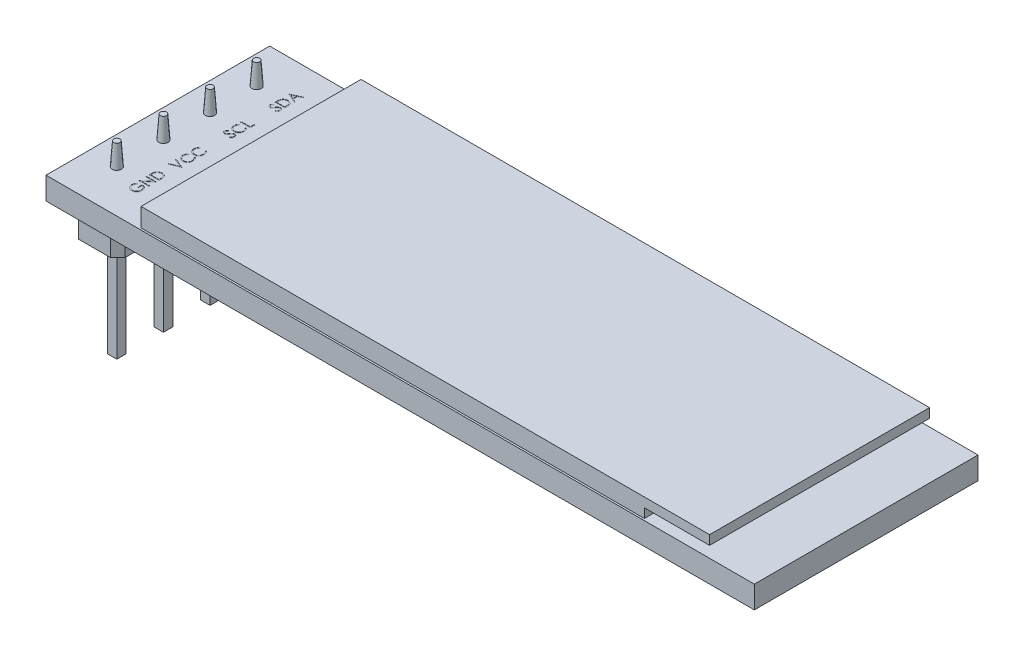
SolidWorks part; units mm, degrees
ref_plane "Alzado" through (0, 0, 0) normal (0, 0, 1) x (1, 0, 0)
ref_plane "Planta" through (0, 0, 0) normal (0, 1, 0) x (1, 0, 0)
ref_plane "Vista lateral" through (0, 0, 0) normal (1, 0, 0) x (0, 0, -1)
sketch "Croquis1" plane through (0, 0, 0) normal (0, 1, 0) x (1, 0, 0)
  line L1 (-19, 6) -> (19, 6)
  line L2 (-19, 6) -> (-19, -6)
  line L3 (-19, -6) -> (19, -6)
  line L4 (19, 6) -> (19, -6)
  line L5 (-19, 6) -> (19, -6) construction
  line L6 (-19, -6) -> (19, 6) construction
  point P0 (0, 0)
  dimension "D1" = 38
  dimension "D2" = 12
extrude "Saliente-Extruir1" add sketch "Croquis1" along normal blind 1.2
sketch "Croquis2" plane through (0, 1.2, 0) normal (0, 1, 0) x (1, 0, 0)
  line L0 (19, 6) -> (-19, 6) construction
  line L1 (-19, 6) -> (-19, -6) construction
  circle A0 centre (-17.5, 3.8) radius 0.25
  circle A1 centre (-17.5, 1.3) radius 0.25
  circle A2 centre (-17.5, -1.2) radius 0.25
  circle A3 centre (-17.5, -3.7) radius 0.25
  dimension "D1" = 0.5
  dimension "D2" = 2.2
  dimension "D3" = 1.5
  dimension "D4" = 4
extrude "Saliente-Extruir2" add sketch "Croquis2" along normal blind 1.2 draft 4
sketch "Croquis3" plane through (0, 0, 0) normal (0, -1, 0) x (1, 0, 0)
  line L1 (-18.75, -5) -> (-16.25, -5)
  line L2 (-18.75, -5) -> (-18.75, -2.6)
  line L3 (-18.75, -2.6) -> (-16.25, -2.6)
  line L4 (-16.25, -5) -> (-16.25, -2.6)
  line L5 (-18.75, -5) -> (-16.25, -2.6) construction
  line L6 (-18.75, -2.6) -> (-16.25, -5) construction
  point P0 (-17.5, -3.8)
  dimension "D1" = 2.4
  dimension "D2" = 2.5
extrude "Saliente-Extruir3" add sketch "Croquis3" along normal blind 2 contours L2 L1 L4 L3
pattern_linear "MatrizL1" count 4 spacing 2.5 along (0, 0, 1) of "Saliente-Extruir3"
sketch "Croquis4" plane through (0, -2, 0) normal (0, -1, 0) x (1, 0, 0)
  line L0 (-17.75, -1.55) -> (-17.75, -1.05)
  line L1 (-17.75, -4.05) -> (-17.25, -4.05)
  line L2 (-17.75, -4.05) -> (-17.75, -3.55)
  line L3 (-17.75, -3.55) -> (-17.25, -3.55)
  line L4 (-17.25, -4.05) -> (-17.25, -3.55)
  line L5 (-17.75, -4.05) -> (-17.25, -3.55) construction
  line L6 (-17.75, -3.55) -> (-17.25, -4.05) construction
  line L7 (-17.75, -1.55) -> (-17.25, -1.55)
  line L8 (-17.25, -1.55) -> (-17.25, -1.05)
  line L9 (-17.75, -1.05) -> (-17.25, -1.05)
  line L10 (-17.75, 0.95) -> (-17.75, 1.45)
  line L11 (-17.75, 0.95) -> (-17.25, 0.95)
  line L12 (-17.25, 0.95) -> (-17.25, 1.45)
  line L13 (-17.75, 1.45) -> (-17.25, 1.45)
  line L14 (-17.75, 3.45) -> (-17.75, 3.95)
  line L15 (-17.75, 3.45) -> (-17.25, 3.45)
  line L16 (-17.25, 3.45) -> (-17.25, 3.95)
  line L17 (-17.75, 3.95) -> (-17.25, 3.95)
  point P0 (-17.5, -3.8)
  dimension "D1" = 0.5
  dimension "D2" = 0.5
  dimension "D3" = 4
extrude "Saliente-Extruir4" add sketch "Croquis4" along normal blind 5.5
chamfer "Chaflán1" distance 0.4 angle 45 16 edges at (-16.25, -1, 4.9) (-16.25, -1, 2.5) (-16.25, -1, 2.4) (-16.25, -1, 0) (-18.75, -1, 4.9) (-18.75, -1, 2.5) (-18.75, -1, 2.4) (-18.75, -1, 0) (-18.75, -1, -0.1) (-18.75, -1, -2.5) (-18.75, -1, -2.6) (-16.25, -1, -0.1) (-16.25, -1, -2.5) (-16.25, -1, -2.6) (-16.25, -1, -5) (-18.75, -1, -5)
sketch "Croquis5" plane through (0, 0, 0) normal (0, -1, 0) x (1, 0, 0)
  line L0 (19, -6) -> (-19, -6) construction
  line L1 (4.5, -5.3) -> (3, -5.3)
  line L2 (4.5, -5.3) -> (4.5, -4.5)
  line L3 (4.5, -4.5) -> (3, -4.5)
  line L4 (3, -5.3) -> (3, -4.5)
  line L5 (4.5, -5.3) -> (3, -4.5) construction
  line L6 (4.5, -4.5) -> (3, -5.3) construction
  line L7 (19, 6) -> (19, -6) construction
  line L8 (4.5, -3.9) -> (4.5, -3.1)
  line L9 (4.5, -3.9) -> (3, -3.9)
  line L10 (3, -3.9) -> (3, -3.1)
  line L11 (4.5, -3.1) -> (3, -3.1)
  line L12 (4.5, -2.5) -> (4.5, -1.7)
  line L13 (4.5, -2.5) -> (3, -2.5)
  line L14 (3, -2.5) -> (3, -1.7)
  line L15 (4.5, -1.7) -> (3, -1.7)
  line L16 (4.5, -1.1) -> (4.5, -0.3)
  line L17 (4.5, -1.1) -> (3, -1.1)
  line L18 (3, -1.1) -> (3, -0.3)
  line L19 (4.5, -0.3) -> (3, -0.3)
  line L20 (4.5, 0.3) -> (4.5, 1.1)
  line L21 (4.5, 0.3) -> (3, 0.3)
  line L22 (3, 0.3) -> (3, 1.1)
  line L23 (4.5, 1.1) -> (3, 1.1)
  line L24 (4.5, 1.7) -> (4.5, 2.5)
  line L25 (4.5, 1.7) -> (3, 1.7)
  line L26 (3, 1.7) -> (3, 2.5)
  line L27 (4.5, 2.5) -> (3, 2.5)
  line L28 (4.5, 3.1) -> (4.5, 3.9)
  line L29 (4.5, 3.1) -> (3, 3.1)
  line L30 (3, 3.1) -> (3, 3.9)
  line L31 (4.5, 3.9) -> (3, 3.9)
  line L32 (4.5, 4.5) -> (4.5, 5.3)
  line L33 (4.5, 4.5) -> (3, 4.5)
  line L34 (3, 4.5) -> (3, 5.3)
  line L35 (4.5, 5.3) -> (3, 5.3)
  line L36 (-2, -1.9) -> (-2, -1.1)
  line L37 (-2, -3.3) -> (-3.5, -3.3)
  line L38 (-2, -3.3) -> (-2, -2.5)
  line L39 (-2, -2.5) -> (-3.5, -2.5)
  line L40 (-3.5, -3.3) -> (-3.5, -2.5)
  line L41 (-2, -3.3) -> (-3.5, -2.5) construction
  line L42 (-2, -2.5) -> (-3.5, -3.3) construction
  line L43 (-2, -1.9) -> (-3.5, -1.9)
  line L44 (-3.5, -1.9) -> (-3.5, -1.1)
  line L45 (-2, -1.1) -> (-3.5, -1.1)
  line L46 (-2, -0.5) -> (-2, 0.3)
  line L47 (-2, -0.5) -> (-3.5, -0.5)
  line L48 (-3.5, -0.5) -> (-3.5, 0.3)
  line L49 (-2, 0.3) -> (-3.5, 0.3)
  line L50 (-2, 0.9) -> (-2, 1.7)
  line L51 (-2, 0.9) -> (-3.5, 0.9)
  line L52 (-3.5, 0.9) -> (-3.5, 1.7)
  line L53 (-2, 1.7) -> (-3.5, 1.7)
  line L54 (-2, 2.3) -> (-2, 3.1)
  line L55 (-2, 2.3) -> (-3.5, 2.3)
  line L56 (-3.5, 2.3) -> (-3.5, 3.1)
  line L57 (-2, 3.1) -> (-3.5, 3.1)
  point P0 (3.75, -4.9)
  point P9 (-2.75, -2.9)
  dimension "D1" = 0.7
  dimension "D2" = 0.8
  dimension "D3" = 14.5
  dimension "D4" = 1.5
  dimension "D5" = 8
  dimension "D6" = 5
  dimension "D7" = 2.7
  dimension "D8" = 1.5
  dimension "D9" = 0.8
  dimension "D10" = 5
extrude "Saliente-Extruir5" add sketch "Croquis5" along normal blind 0.7 separate body
sketch "Croquis6" plane through (0, -0.7, 0) normal (0, -1, 0) x (1, 0, 0)
  line L0 (3, -0.3) -> (3, -1.1) construction
  line L1 (4.5, -1.1) -> (3, -1.1)
  line L2 (4.5, -1.1) -> (4.5, -0.3)
  line L3 (4.5, -0.3) -> (3, -0.3)
  line L4 (3, -1.1) -> (3, -0.3)
  line L5 (4.5, -1.1) -> (3, -0.3) construction
  line L6 (4.5, -0.3) -> (3, -1.1) construction
  line L7 (4.5, -0.3) -> (3, -0.3) construction
  line L8 (-2, -2.5) -> (-3.5, -2.5) construction
  line L9 (-2, -3.3) -> (-3.5, -3.3)
  line L10 (-2, -3.3) -> (-2, -2.5)
  line L11 (-2, -2.5) -> (-3.5, -2.5)
  line L12 (-3.5, -3.3) -> (-3.5, -2.5)
  line L13 (-2, -3.3) -> (-3.5, -2.5) construction
  line L14 (-2, -2.5) -> (-3.5, -3.3) construction
  line L15 (-3.5, -2.5) -> (-3.5, -3.3) construction
  line L16 (-3.5, 0.3) -> (-3.5, -0.5) construction
  line L17 (-2, -1.9) -> (-3.5, -1.9)
  line L18 (-2, -1.9) -> (-2, -1.1)
  line L19 (-2, -1.1) -> (-3.5, -1.1)
  line L20 (-3.5, -1.9) -> (-3.5, -1.1)
  line L21 (-2, -1.9) -> (-3.5, -1.1) construction
  line L22 (-2, -1.1) -> (-3.5, -1.9) construction
  line L23 (-2, -0.5) -> (-3.5, -0.5)
  line L24 (-2, -0.5) -> (-2, 0.3)
  line L25 (-2, 0.3) -> (-3.5, 0.3)
  line L26 (-3.5, -0.5) -> (-3.5, 0.3)
  line L27 (-2, -0.5) -> (-3.5, 0.3) construction
  line L28 (-2, 0.3) -> (-3.5, -0.5) construction
  line L29 (-2, 0.3) -> (-3.5, 0.3) construction
  point P0 (3.75, -0.7)
  point P9 (-2.75, -2.9)
  point P18 (-2.75, -1.5)
  point P24 (-2.75, -0.1)
extrude "Cortar-Extruir1" cut sketch "Croquis6" against normal blind 0.4
sketch "Croquis7" plane through (0, -0.7, 0) normal (0, -1, 0) x (1, 0, 0)
  line L0 (-2.75, 1.7) -> (-2.75, 1.0081) construction
  line L1 (-2, 1.7) -> (-3.5, 1.7) construction
  line L2 (-2, 1.3) -> (-2.9455, 1.3) construction
  line L3 (-2, 0.9) -> (-2, 1.7) construction
  line L4 (-3.5, 0.9) -> (-2, 0.9) construction
  line L5 (-3.5, 1.7) -> (-2, 1.7)
  line L6 (-3.5, 1.7) -> (-3.5, 0.9)
  line L7 (-3.5, 0.9) -> (-2, 0.9)
  line L8 (-2, 1.7) -> (-2, 0.9)
  line L9 (-3.5, 1.7) -> (-2, 0.9) construction
  line L10 (-3.5, 0.9) -> (-2, 1.7) construction
  point P8 (-2.75, 1.3)
extrude "Cortar-Extruir2" cut sketch "Croquis7" against normal blind 0.3
sketch "Croquis8" plane through (0, 0, 0) normal (0, -1, 0) x (1, 0, 0)
  line L0 (-19, 6) -> (19, 6) construction
  line L1 (-9.5, 0.5) -> (-10.5, 0.5)
  line L2 (-9.5, 0.5) -> (-9.5, 3)
  line L3 (-9.5, 3) -> (-10.5, 3)
  line L4 (-10.5, 0.5) -> (-10.5, 3)
  line L5 (-9.5, 0.5) -> (-10.5, 3) construction
  line L6 (-9.5, 3) -> (-10.5, 0.5) construction
  line L7 (-19, -6) -> (-19, 6) construction
  point P0 (-10, 1.75)
  dimension "D1" = 3
  dimension "D2" = 8.5
  dimension "D3" = 2.5
  dimension "D4" = 1
extrude "Saliente-Extruir6" add sketch "Croquis8" along normal blind 1
ref_plane "Plano1" through (0, 0, 0.62) normal (0, 0, 1) x (1, 0, 0)
sketch "Croquis9" plane through (0, 0, 0.62) normal (0, 0, 1) x (1, 0, 0)
  line L0 (-9.5, -0.2801) -> (-9.3251, -0.2801)
  line L1 (-9.5, -1) -> (-9.5, 0) construction
  line L2 (-9.3051, -0.2601) -> (-9.3051, 0)
  line L3 (-19, 0) -> (19, 0) construction
  line L4 (-9.5, -0.2432) -> (-9.3639, -0.2432)
  line L5 (-9.3439, -0.2232) -> (-9.3439, 0)
  line L6 (-9.5, -0.2432) -> (-9.5, -0.2801)
  line L7 (-9.3439, 0) -> (-9.3051, 0)
  arc A0 (-9.3051, -0.2601) -> (-9.3251, -0.2801) centre (-9.3251, -0.2601) cw
  arc A1 (-9.3639, -0.2432) -> (-9.3439, -0.2232) centre (-9.3639, -0.2232) ccw
  dimension "D1" = 0.02
extrude "Saliente-Extruir7" add sketch "Croquis9" along normal blind 0.9
pattern_linear "MatrizL2" count 2 spacing 1.3 along (0, 0, 1) of "Saliente-Extruir7"
ref_plane "Plano2" through (0, 0, 1.75) normal (0, 0, 1) x (1, 0, 0)
sketch "Croquis12" plane through (0, 0, 1.75) normal (0, 0, 1) x (1, 0, 0)
  line L1 (-10.5, -0.2801) -> (-10.5, -0.2432)
  line L6 (-10, 0) -> (-10, -0.6809) construction
  line L7 (-10.5, 0) -> (-9.5, 0) construction
  line L8 (-10.6949, 0) -> (-10.6561, 0)
  line L10 (-10.5, -0.2801) -> (-10.6949, -0.2801)
  line L11 (-10.5, -0.2432) -> (-10.6561, -0.2432)
  line L12 (-10.6561, 0) -> (-10.6561, -0.2432)
  line L13 (-10.6949, -0.2801) -> (-10.6949, 0)
  point P0 (-10.6538, -0.2432)
extrude "Saliente-Extruir8" add sketch "Croquis12" along normal blind 0.45 and the other way blind 0.45
sketch "Croquis13" plane through (0, 1.2, 0) normal (0, 1, 0) x (1, 0, 0)
  line L0 (-14, 5.9) -> (13, 5.9)
  line L1 (13, 5.9) -> (13, -5.9)
  line L2 (13, -5.9) -> (-14, -5.9)
  line L3 (-14, -5.9) -> (-14, 5.9)
  line L4 (-19, 6) -> (-19, -6) construction
  line L5 (19, 6) -> (-19, 6) construction
  line L6 (-19, -6) -> (19, -6) construction
  line L7 (19, -6) -> (19, 6) construction
  dimension "D1" = 5
  dimension "D2" = 0.1
  dimension "D3" = 0.1
  dimension "D4" = 6
extrude "Saliente-Extruir9" add sketch "Croquis13" along normal blind 0.5 separate body
sketch "Croquis14" plane through (0, 1.7, 0) normal (0, 1, 0) x (1, 0, 0)
  line L0 (-14, 5.9) -> (-14, -5.9)
  line L1 (-14, -5.9) -> (16.5, -5.9)
  line L2 (16.5, -5.9) -> (16.5, 5.9)
  line L3 (16.5, 5.9) -> (-14, 5.9)
  line L4 (19, -6) -> (19, 6) construction
  dimension "D1" = 2.5
extrude "Saliente-Extruir10" add sketch "Croquis14" along normal blind 0.5
sketch "Croquis15" plane through (0, 1.2, 0) normal (0, 1, 0) x (1, 0, 0)
  line L0 (-15.7156, -4.4709) -> (-15.7156, -2.4648) construction
  line L2 (-15.7156, -2.2499) -> (-15.7156, 0) construction
  line L4 (-15.7156, 0.6476) -> (-15.7156, 2.0322) construction
  line L6 (-15.7156, 3.0934) -> (-15.7156, 4.6423) construction
  text T0 "GND" font "Century Gothic" height in points 2
  text T1 "VCC" font "Century Gothic" height in points 2
  text T2 "SCL" font "Century Gothic" height in points 2
  text T3 "SDA" font "Century Gothic" height in points 2
  point P9 (-15.7086, -2.4648)
  point P10 (-15.7364, -2.0611)
  point P11 (-15.7152, 0.2341)
  point P12 (-15.7344, -2.2499)
  point P14 (-15.713, 4.6423)
  point P15 (-15.7241, 2.8745)
  point P16 (-15.7288, 3.0934)
  point P17 (-15.7156, 0.4837)
  point P18 (-15.7156, 0.6476)
extrude "Cortar-Extruir3" cut sketch "Croquis15" against normal blind 0.01
fillet "Redondeo1" radius 0.1 8 edges at (3, -0.35, -4.5) (3, -0.7, -4.9) (3, -0.35, -5.3) (3, 0, -4.9) (4.5, -0.35, -5.3) (4.5, -0.7, -4.9) (4.5, -0.35, -4.5) (4.5, 0, -4.9)
fillet "Redondeo2" radius 0.1 8 edges at (3, -0.35, -3.1) (3, -0.7, -3.5) (3, -0.35, -3.9) (3, 0, -3.5) (4.5, -0.35, -3.9) (4.5, -0.7, -3.5) (4.5, -0.35, -3.1) (4.5, 0, -3.5)
fillet "Redondeo3" radius 0.1 8 edges at (4.5, -0.35, -2.5) (4.5, -0.7, -2.1) (4.5, -0.35, -1.7) (4.5, 0, -2.1) (3, -0.35, -1.7) (3, -0.7, -2.1) (3, -0.35, -2.5) (3, 0, -2.1)
fillet "Redondeo4" radius 0.1 8 edges at (4.5, -0.35, 0.3) (4.5, -0.7, 0.7) (4.5, -0.35, 1.1) (4.5, 0, 0.7) (3, -0.35, 1.1) (3, -0.7, 0.7) (3, -0.35, 0.3) (3, 0, 0.7)
fillet "Redondeo5" radius 0.1 8 edges at (4.5, -0.35, 1.7) (4.5, -0.7, 2.1) (4.5, -0.35, 2.5) (4.5, 0, 2.1) (3, -0.35, 2.5) (3, -0.7, 2.1) (3, -0.35, 1.7) (3, 0, 2.1)
fillet "Redondeo6" radius 0.1 8 edges at (4.5, -0.35, 3.1) (4.5, -0.7, 3.5) (4.5, -0.35, 3.9) (4.5, 0, 3.5) (3, -0.35, 3.9) (3, -0.7, 3.5) (3, -0.35, 3.1) (3, 0, 3.5)
fillet "Redondeo7" radius 0.1 8 edges at (4.5, -0.35, 4.5) (4.5, -0.7, 4.9) (4.5, -0.35, 5.3) (4.5, 0, 4.9) (3, -0.35, 5.3) (3, -0.7, 4.9) (3, -0.35, 4.5) (3, 0, 4.9)
fillet "Redondeo8" radius 0.1 8 edges at (-3.5, -0.35, 3.1) (-3.5, -0.7, 2.7) (-3.5, -0.35, 2.3) (-3.5, 0, 2.7) (-2, -0.35, 2.3) (-2, -0.7, 2.7) (-2, -0.35, 3.1) (-2, 0, 2.7)
fillet "Redondeo9" radius 0.1 8 edges at (4.5, -0.15, -0.3) (4.5, 0, -0.7) (4.5, -0.15, -1.1) (4.5, -0.3, -0.7) (3, -0.15, -1.1) (3, 0, -0.7) (3, -0.15, -0.3) (3, -0.3, -0.7)
fillet "Redondeo10" radius 0.1 8 edges at (-3.5, -0.15, -3.3) (-3.5, 0, -2.9) (-3.5, -0.15, -2.5) (-3.5, -0.3, -2.9) (-2, -0.15, -2.5) (-2, 0, -2.9) (-2, -0.15, -3.3) (-2, -0.3, -2.9)
fillet "Redondeo11" radius 0.1 8 edges at (-2, -0.15, -1.1) (-2, 0, -1.5) (-2, -0.15, -1.9) (-2, -0.3, -1.5) (-3.5, -0.15, -1.9) (-3.5, 0, -1.5) (-3.5, -0.15, -1.1) (-3.5, -0.3, -1.5)
fillet "Redondeo12" radius 0.1 8 edges at (-2, -0.15, 0.3) (-2, 0, -0.1) (-2, -0.15, -0.5) (-2, -0.3, -0.1) (-3.5, -0.15, -0.5) (-3.5, 0, -0.1) (-3.5, -0.15, 0.3) (-3.5, -0.3, -0.1)
sketch "Croquis16" plane through (0, 0, 0) normal (0, -1, 0) x (1, 0, 0)
  line L0 (2.7698, -4.5585) -> (1.3056, -4.5585) construction
  line L1 (2.7698, -3.1585) -> (1.3056, -3.1585) construction
  line L2 (2.7698, -1.7585) -> (1.3056, -1.7585) construction
  line L3 (2.7698, -0.3585) -> (1.3056, -0.3585) construction
  line L4 (2.7698, 1.0415) -> (1.3056, 1.0415) construction
  line L5 (2.7698, 2.4415) -> (1.3056, 2.4415) construction
  line L6 (2.7698, 3.8415) -> (1.3056, 3.8415) construction
  line L7 (2.7698, 5.2415) -> (1.3056, 5.2415) construction
  line L8 (-3.7045, -2.5778) -> (-5.3272, -2.5778) construction
  line L9 (-3.7045, -1.1778) -> (-5.3272, -1.1778) construction
  line L10 (-3.7045, 0.2222) -> (-5.3272, 0.2222) construction
  line L11 (-3.7045, 1.6222) -> (-5.3272, 1.6222) construction
  line L12 (-3.7045, 3.0222) -> (-5.3272, 3.0222) construction
  line L14 (-10.7639, 2.3852) -> (-10.7639, 3.623) construction
  text T0 "C9" font "Century Gothic" height in points 2
  text T1 "C6" font "Century Gothic" height in points 2
  text T2 "C4" font "Century Gothic" height in points 2
  text T3 "R1" font "Century Gothic" height in points 2
  text T4 "C10" font "Century Gothic" height in points 2
  text T5 "C5" font "Century Gothic" height in points 2
  text T6 "C2" font "Century Gothic" height in points 2
  text T7 "C1" font "Century Gothic" height in points 2
  text T8 "R4" font "Century Gothic" height in points 2
  text T9 "R3" font "Century Gothic" height in points 2
  text T10 "R9" font "Century Gothic" height in points 2
  text T11 "D1" font "Century Gothic" height in points 2
  text T12 "C11" font "Century Gothic" height in points 2
  text T13 "U2" font "Century Gothic" height in points 2
  point P18 (-10.7803, 2.3852)
  point P19 (-10.7639, 3.623)
  dimension "D1" = 8
  dimension "D2" = 5
extrude "Cortar-Extruir4" cut sketch "Croquis16" against normal blind 0.01
